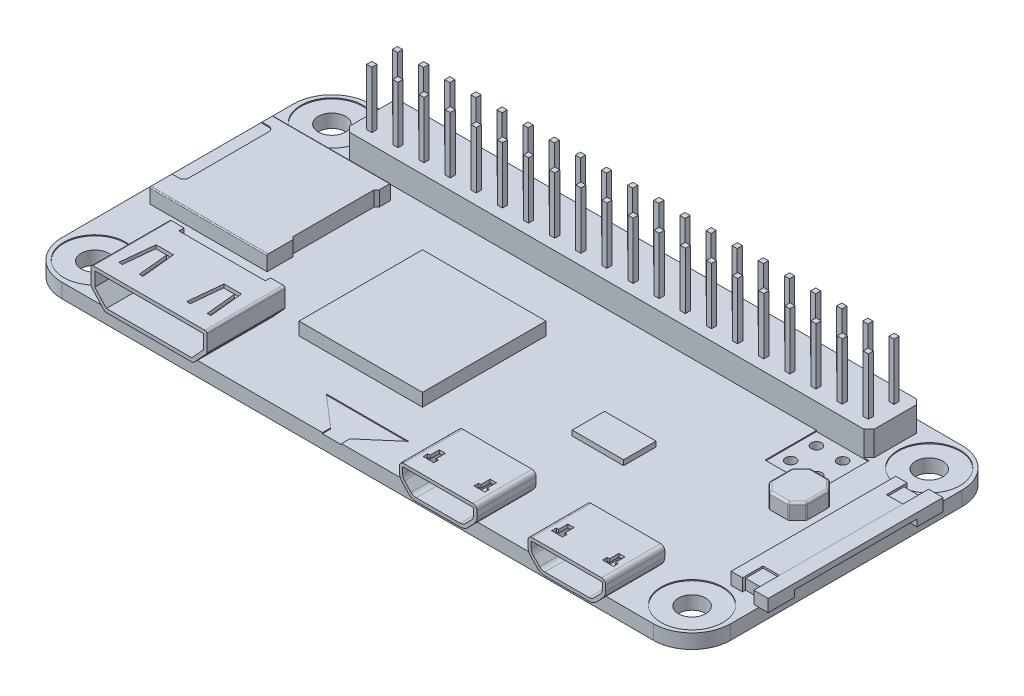
SolidWorks part; units mm, degrees
ref_plane "Front Plane" through (0, 0, 0) normal (0, 0, 1) x (1, 0, 0)
ref_plane "Top Plane" through (0, 0, 0) normal (0, 1, 0) x (1, 0, 0)
ref_plane "Right Plane" through (0, 0, 0) normal (1, 0, 0) x (0, 0, -1)
sketch "Sketch1" plane through (0, 0, 0) normal (0, 1, 0) x (1, 0, 0)
  line L1 (-28.75, 15) -> (28.75, 15)
  line L2 (-32.5, 11.25) -> (-32.5, -11.25)
  line L3 (-28.75, -15) -> (28.75, -15)
  line L4 (32.5, 11.25) -> (32.5, -11.25)
  line L5 (-32.5, 15) -> (32.5, -15) construction
  line L6 (-32.5, -15) -> (32.5, 15) construction
  arc A0 (-32.5, -11.25) -> (-28.75, -15) centre (-28.75, -11.25) ccw
  arc A1 (28.75, -15) -> (32.5, -11.25) centre (28.75, -11.25) ccw
  arc A2 (28.75, 15) -> (32.5, 11.25) centre (28.75, 11.25) cw
  arc A3 (-28.75, 15) -> (-32.5, 11.25) centre (-28.75, 11.25) ccw
  point P0 (0, 0)
  dimension "D3" = 3.75
  dimension "D1" = 65
  dimension "D2" = 30
extrude "Boss-Extrude1" add sketch "Sketch1" along normal blind 1.4 contours L1 A2 L4 A1 L3 A0 L2 A3
sketch "Sketch2" plane through (0, 1.4, 0) normal (0, 1, 0) x (1, 0, 0)
  line L0 (0, 15) -> (0, -15) construction
  line L1 (-28.75, 15) -> (28.75, 15) construction
  line L2 (-28.75, -15) -> (28.75, -15) construction
  line L3 (-32.5, 0) -> (32.5, 0) construction
  line L4 (-32.5, 11.25) -> (-32.5, -11.25) construction
  line L5 (32.5, 11.25) -> (32.5, -11.25) construction
  circle A0 centre (-29.025, 11.525) radius 1.325
  circle A2 centre (29.025, 11.525) radius 1.325
  circle A3 centre (29.025, -11.525) radius 1.325
  circle A4 centre (-29.025, -11.525) radius 1.325
  dimension "D1" = 2.65
  dimension "D2" = 2.15
  dimension "D3" = 2.15
extrude "Cut-Extrude1" cut sketch "Sketch2" against normal through all
sketch "Sketch3" plane through (0, 1.4, 0) normal (0, 1, 0) x (1, 0, 0)
  line L0 (-24.128, 13) -> (-24.128, 10.5) construction
  line L3 (-28.75, 15) -> (28.75, 15) construction
  line L5 (-32.5, 11.25) -> (-32.5, -11.25) construction
  circle A0 centre (-24.128, 13) radius 0.5
  circle A1 centre (-24.128, 10.5) radius 0.5
  dimension "D1" = 1
  dimension "D3" = 1.5
  dimension "D4" = 7.872
  dimension "D2" = 2.5
extrude "Cut-Extrude2" cut sketch "Sketch3" against normal through all
pattern_linear "LPattern1" count 20 spacing 2.54 along (1, 0, 0) of "Cut-Extrude2"
sketch "Sketch5" plane through (0, 1.4, 0) normal (0, 1, 0) x (1, 0, 0)
  line L0 (21.592, 10.5) -> (21.592, 5.5) construction
  line L1 (24.132, 10.5) -> (24.132, 5.5) construction
  line L2 (24.132, 5.5) -> (21.592, 5.5) construction
  circle A0 centre (21.592, 5.5) radius 0.5
  circle A1 centre (24.132, 5.5) radius 0.5
  circle A2 centre (21.592, 8) radius 0.5
  circle A3 centre (24.132, 8) radius 0.5
  dimension "D1" = 2.5
  dimension "D2" = 1
extrude "Cut-Extrude4" cut sketch "Sketch5" against normal through all
sketch "Sketch4" plane through (0, 1.4, 0) normal (0, 1, 0) x (1, 0, 0)
  line L0 (0, 0) -> (0, 14.3) construction
  line L1 (-24.128, 13) -> (-24.128, 10.5) construction
  line L2 (-25.5, 14.3) -> (25.5, 14.3)
  line L3 (-25.5, 14.3) -> (-25.5, 9.2)
  line L4 (-25.5, 9.2) -> (20.4, 9.2)
  line L5 (25.5, 14.3) -> (25.5, 9.2)
  line L6 (-25.5, 11.75) -> (-24.128, 11.75) construction
  line L7 (20.4, 9.2) -> (25.5, 9.2) construction
  line L8 (-2.5, -15) -> (-2.5, -11.55) construction
  line L9 (25.5, 9.2) -> (25.5, 4.2)
  line L10 (25.5, 4.2) -> (20.4, 4.2)
  line L11 (20.4, 9.2) -> (20.4, 4.2)
  line L12 (-28.75, -15) -> (28.75, -15) construction
  line L13 (-6.5, -11.55) -> (1.5, -11.55)
  line L14 (1.5, -11.55) -> (-1.575, -14.2)
  line L15 (-1.575, -14.2) -> (-1.575, -15)
  line L16 (-1.575, -15) -> (-3.425, -15)
  line L17 (-3.425, -15) -> (-3.425, -14.2)
  line L18 (-3.425, -14.2) -> (-6.5, -11.55)
  line L19 (-32.5, 11.25) -> (-32.5, -11.25) construction
  circle A0 centre (-29.025, 11.525) radius 3
  circle A1 centre (-29.025, -11.525) radius 3
  circle A2 centre (29.025, -11.525) radius 3
  circle A3 centre (29.025, 11.525) radius 3
  point P23 (-24.128, 11.75)
  point P26 (-25.5, 11.75)
  dimension "D1" = 6
  dimension "D2" = 5.1
  dimension "D3" = 51
  dimension "D4" = 5.1
  dimension "D5" = 5
  dimension "D6" = 8
  dimension "D7" = 1.85
  dimension "D8" = 3.45
  dimension "D9" = 0.8
  dimension "D10" = 30
extrude "Cut-Extrude3" cut sketch "Sketch4" against normal blind 0.1
sketch "Sketch6" plane through (0, 1.4, 0) normal (0, 1, 0) x (1, 0, 0)
  line L0 (-28.75, -15) -> (-3.425, -15) construction
  line L1 (-12.7, 4) -> (-0.7, 4)
  line L2 (-12.7, 4) -> (-12.7, -8)
  line L3 (-12.7, -8) -> (-0.7, -8)
  line L4 (-0.7, 4) -> (-0.7, -8)
  line L5 (-12.7, 4) -> (-0.7, -8) construction
  line L6 (-12.7, -8) -> (-0.7, 4) construction
  line L7 (-32.5, 11.25) -> (-32.5, -11.25) construction
  point P0 (-6.7, -2)
  dimension "D1" = 12
  dimension "D2" = 7
  dimension "D3" = 19.8
extrude "Boss-Extrude2" add sketch "Sketch6" along normal blind 1.25
sketch "Sketch7" plane through (0, 1.4, 0) normal (0, 1, 0) x (1, 0, 0)
  line L0 (-19.65, 7.85) -> (-19.65, 6.75)
  line L1 (-31.05, 7.85) -> (-19.65, 7.85)
  line L2 (-31.05, 7.85) -> (-31.05, -4.15) construction
  line L3 (-31.05, -4.15) -> (-19.65, -4.15)
  line L4 (-19.65, 7.85) -> (-19.65, -4.15) construction
  line L5 (-19.65, 6.75) -> (-19.9, 6.5)
  line L6 (-19.9, 6.5) -> (-19.9, -1.4)
  line L7 (-19.9, -1.4) -> (-19.65, -1.65)
  line L8 (-19.65, -1.65) -> (-19.65, -4.15)
  line L9 (-31.05, 7.85) -> (-31.05, 6.75)
  line L10 (-31.05, 6.75) -> (-30.4, 6.75)
  line L11 (-29.9, 6.25) -> (-29.9, -1.5)
  line L12 (-30.4, -2) -> (-31.05, -2)
  line L13 (-31.05, -2) -> (-31.05, -4.15)
  line L14 (-28.75, 15) -> (28.75, 15) construction
  line L15 (-32.5, 11.25) -> (-32.5, -11.25) construction
  arc A0 (-29.9, -1.5) -> (-30.4, -2) centre (-30.4, -1.5) cw
  arc A1 (-30.4, 6.75) -> (-29.9, 6.25) centre (-30.4, 6.25) cw
  dimension "D9" = 0.5
  dimension "D1" = 11.4
  dimension "D2" = 12
  dimension "D3" = 2.5
  dimension "D4" = 1.1
  dimension "D5" = 0.25
  dimension "D6" = 1.1
  dimension "D7" = 2.15
  dimension "D8" = 1.15
  dimension "D10" = 7.15
  dimension "D11" = 1.45
extrude "Boss-Extrude3" add sketch "Sketch7" along normal blind 1.45
fillet "Fillet2" radius 0.1 2 edges at (-25.35, 2.85, -7.85) (-25.35, 2.85, 4.15)
sketch "Sketch8" plane through (-29.9, 0, 0) normal (-1, 0, 0) x (0, 0, 1)
  line L0 (-7.85, 2.75) -> (-7.85, 1.4) construction
  line L1 (-7.75, 2.75) -> (4.05, 2.75)
  line L2 (-7.75, 2.75) -> (-7.75, 1.5)
  line L3 (-7.75, 1.5) -> (4.05, 1.5)
  line L4 (4.05, 2.75) -> (4.05, 1.5)
  line L5 (-6.25, 2.85) -> (1.5, 2.85) construction
  line L6 (4.15, 2.75) -> (4.15, 1.4) construction
  line L7 (-6.25, 1.4) -> (1.5, 1.4) construction
  dimension "D1" = 0.1
  dimension "D2" = 0.1
  dimension "D3" = 0.1
  dimension "D4" = 0.1
extrude "Cut-Extrude5" cut sketch "Sketch8" against normal blind 9.5 and the other way through all
sketch "Sketch9" plane through (0, 0, 15) normal (0, 0, 1) x (1, 0, 0)
  line L0 (-19.875, 1.4) -> (-19.875, 4.7) construction
  line L1 (-28.75, 1.4) -> (-3.425, 1.4) construction
  line L2 (-25.5, 4.7) -> (-14.25, 4.7)
  line L3 (-14.25, 4.7) -> (-14.25, 2.85)
  line L4 (-14.25, 2.85) -> (-15.575, 1.4)
  line L5 (-12.7, 1.4) -> (-0.7, 1.4) construction
  line L6 (-15.575, 1.4) -> (-24.175, 1.4)
  line L7 (-24.175, 1.4) -> (-25.5, 2.85)
  line L8 (-25.5, 2.85) -> (-25.5, 4.7)
  line L9 (-32.5, 1.4) -> (-32.5, 0) construction
  dimension "D1" = 3.3
  dimension "D2" = 1.85
  dimension "D3" = 8.6
  dimension "D4" = 11.25
  dimension "D5" = 7
extrude "Boss-Extrude4" add sketch "Sketch9" along normal blind 0.4 and the other way blind 7.2 separate body
fillet "Fillet1" radius 0.2 6 edges at (-15.575, 1.4, 11.6) (-24.175, 1.4, 11.6) (-25.5, 2.85, 11.6) (-14.25, 2.85, 11.6) (-25.5, 4.7, 11.6) (-14.25, 4.7, 11.6)
sketch "Sketch10" plane through (0, 0, 15.4) normal (0, 0, 1) x (1, 0, 0)
  line L12 (-25.15, 4.35) -> (-25.15, 2.9858)
  line L13 (-25.15, 2.9858) -> (-24.0207, 1.75)
  line L14 (-24.0207, 1.75) -> (-15.7293, 1.75)
  line L15 (-15.7293, 1.75) -> (-14.6, 2.9858)
  line L16 (-14.6, 2.9858) -> (-14.6, 4.35)
  line L17 (-14.6, 4.35) -> (-25.15, 4.35)
  line L18 (-25.15, 4.35) -> (-25.15, 2.9858)
  line L19 (-25.15, 2.9858) -> (-24.0207, 1.75)
  line L20 (-24.0207, 1.75) -> (-15.7293, 1.75)
  line L21 (-15.7293, 1.75) -> (-14.6, 2.9858)
  line L22 (-14.6, 2.9858) -> (-14.6, 4.35)
  line L23 (-14.6, 4.35) -> (-25.15, 4.35)
  dimension "D1" = 0.35
extrude "Cut-Extrude6" cut sketch "Sketch10" against normal blind 7
sketch "Sketch11" plane through (0, 0, 8.4) normal (0, 0, 1) x (1, 0, 0)
  line L0 (-19.875, 3.5) -> (-19.875, 1.75) construction
  line L1 (-23.375, 2.95) -> (-16.375, 2.95)
  line L2 (-23.375, 2.95) -> (-23.375, 3.5)
  line L3 (-23.375, 3.5) -> (-16.375, 3.5)
  line L4 (-16.375, 2.95) -> (-16.375, 3.5)
  line L5 (-24.0207, 1.75) -> (-15.7293, 1.75) construction
  line L6 (-24.0207, 1.75) -> (-15.7293, 1.75) construction
  dimension "D1" = 7
  dimension "D2" = 0.55
  dimension "D3" = 1.2
extrude "Boss-Extrude5" add sketch "Sketch11" along normal blind 3.5
sketch "Sketch12" plane through (0, 4.35, 0) normal (0, -1, 0) x (1, 0, 0)
  line L0 (-19.875, 7.8) -> (-19.875, 15.4) construction
  line L1 (-14.45, 7.8) -> (-25.3, 7.8) construction
  line L2 (-14.45, 15.4) -> (-25.3, 15.4) construction
  line L3 (-23.175, 10.57) -> (-23.175, 13.4458) construction
  line L4 (-24.025, 10.57) -> (-22.325, 10.57)
  line L5 (-22.325, 10.57) -> (-22, 13.87)
  line L6 (-22, 13.87) -> (-22.3517, 13.87)
  line L7 (-22.3517, 13.87) -> (-22.6422, 10.92)
  line L8 (-22.6422, 10.92) -> (-23.7078, 10.92)
  line L9 (-23.9983, 13.87) -> (-23.7078, 10.92)
  line L10 (-24.35, 13.87) -> (-23.9983, 13.87)
  line L11 (-24.025, 10.57) -> (-24.35, 13.87)
  line L12 (-16.575, 10.57) -> (-16.575, 13.4458) construction
  line L13 (-15.725, 10.57) -> (-15.4, 13.87)
  line L14 (-15.4, 13.87) -> (-15.7517, 13.87)
  line L15 (-15.7517, 13.87) -> (-16.0422, 10.92)
  line L16 (-17.1078, 10.92) -> (-16.0422, 10.92)
  line L17 (-17.3983, 13.87) -> (-17.1078, 10.92)
  line L18 (-17.75, 13.87) -> (-17.3983, 13.87)
  line L19 (-17.425, 10.57) -> (-17.75, 13.87)
  line L20 (-15.725, 10.57) -> (-17.425, 10.57)
  point P15 (-23.175, 10.92)
  point P28 (-16.575, 10.92)
  dimension "D1" = 0.35
  dimension "D2" = 0.35
  dimension "D3" = 3.3
  dimension "D4" = 2.35
  dimension "D5" = 1.7
  dimension "D6" = 2.77
  dimension "D7" = 4.25
extrude "Cut-Extrude7" cut sketch "Sketch12" against normal through all
sketch "Sketch13" plane through (0, 0, 7.8) normal (0, 0, -1) x (-1, 0, 0)
  line L0 (14.45, 4.7) -> (25.3, 4.7) construction
  line L1 (15.675, 4.7) -> (24.075, 4.7)
  line L2 (15.675, 4.7) -> (15.675, 3.3)
  line L3 (15.675, 3.3) -> (24.075, 3.3)
  line L4 (24.075, 4.7) -> (24.075, 3.3)
  line L5 (19.875, 1.4) -> (19.875, 4.7) construction
  line L6 (24.0868, 1.4) -> (15.6632, 1.4) construction
  dimension "D1" = 8.4
  dimension "D2" = 1.4
extrude "Cut-Extrude8" cut sketch "Sketch13" against normal blind 0.5
sketch "Sketch15" plane through (0, 0, 15) normal (0, 0, 1) x (1, 0, 0)
  line L0 (21.575, 1.4) -> (21.575, 4) construction
  line L1 (-1.575, 1.4) -> (28.75, 1.4) construction
  line L2 (18.2, 4) -> (24.95, 4)
  line L3 (25.35, 3.6) -> (25.35, 3.0523)
  line L4 (25.0714, 2.3598) -> (24.4452, 1.7075)
  line L5 (23.7238, 1.4) -> (19.4262, 1.4)
  line L6 (32.5, 1.4) -> (32.5, 0) construction
  line L7 (18.0786, 2.3598) -> (18.7048, 1.7075)
  line L8 (17.8, 3.6) -> (17.8, 3.0523)
  line L9 (15.325, 0) -> (15.325, 5.5788) construction
  line L10 (-28.75, 0) -> (28.75, 0) construction
  line L11 (9.075, 1.4) -> (9.075, 4) construction
  line L12 (12.85, 3.6) -> (12.85, 3.0523)
  line L13 (12.5714, 2.3598) -> (11.9452, 1.7075)
  line L14 (6.9262, 1.4) -> (11.2238, 1.4)
  line L15 (5.5786, 2.3598) -> (6.2048, 1.7075)
  line L16 (5.3, 3.6) -> (5.3, 3.0523)
  line L17 (12.45, 4) -> (5.7, 4)
  arc A0 (24.4452, 1.7075) -> (23.7238, 1.4) centre (23.7238, 2.4) cw
  arc A1 (18.7048, 1.7075) -> (19.4262, 1.4) centre (19.4262, 2.4) ccw
  arc A2 (25.35, 3.0523) -> (25.0714, 2.3598) centre (24.35, 3.0523) cw
  arc A3 (18.0786, 2.3598) -> (17.8, 3.0523) centre (18.8, 3.0523) cw
  arc A4 (24.95, 4) -> (25.35, 3.6) centre (24.95, 3.6) cw
  arc A5 (17.8, 3.6) -> (18.2, 4) centre (18.2, 3.6) cw
  arc A6 (12.85, 3.6) -> (12.45, 4) centre (12.45, 3.6) ccw
  arc A7 (5.7, 4) -> (5.3, 3.6) centre (5.7, 3.6) ccw
  arc A8 (12.5714, 2.3598) -> (12.85, 3.0523) centre (11.85, 3.0523) ccw
  arc A9 (5.3, 3.0523) -> (5.5786, 2.3598) centre (6.3, 3.0523) ccw
  arc A10 (11.9452, 1.7075) -> (11.2238, 1.4) centre (11.2238, 2.4) cw
  arc A11 (6.2048, 1.7075) -> (6.9262, 1.4) centre (6.9262, 2.4) ccw
  point P14 (24.15, 1.4)
  point P17 (19, 1.4)
  point P20 (25.35, 2.65)
  point P23 (17.8, 2.65)
  point P26 (25.35, 4)
  point P29 (17.8, 4)
  point P54 (12.85, 4)
  point P55 (5.3, 4)
  point P56 (12.85, 2.65)
  point P57 (5.3, 2.65)
  point P58 (11.65, 1.4)
  point P59 (6.5, 1.4)
  dimension "D6" = 1
  dimension "D7" = 0.4
  dimension "D1" = 7.55
  dimension "D2" = 2.6
  dimension "D3" = 1.35
  dimension "D4" = 5.15
  dimension "D5" = 7.15
  dimension "D8" = 4.95
extrude "Boss-Extrude6" add sketch "Sketch15" along normal blind 1.25 and the other way blind 4.5
sketch "Sketch16" plane through (0, 0, 16.25) normal (0, 0, 1) x (1, 0, 0)
  line L12 (12.45, 3.68) -> (5.7, 3.68)
  line L13 (5.62, 3.6) -> (5.62, 3.0523)
  line L14 (5.8095, 2.5814) -> (6.4357, 1.9291)
  line L15 (6.9262, 1.72) -> (11.2238, 1.72)
  line L16 (11.7143, 1.9291) -> (12.3405, 2.5814)
  line L17 (12.53, 3.0523) -> (12.53, 3.6)
  line L18 (12.45, 3.68) -> (5.7, 3.68)
  line L19 (5.62, 3.6) -> (5.62, 3.0523)
  line L20 (5.8095, 2.5814) -> (6.4357, 1.9291)
  line L21 (6.9262, 1.72) -> (11.2238, 1.72)
  line L22 (11.7143, 1.9291) -> (12.3405, 2.5814)
  line L23 (12.53, 3.0523) -> (12.53, 3.6)
  line L30 (24.2143, 1.9291) -> (24.8405, 2.5814)
  line L31 (25.03, 3.0523) -> (25.03, 3.6)
  line L32 (24.95, 3.68) -> (18.2, 3.68)
  line L33 (18.12, 3.6) -> (18.12, 3.0523)
  line L34 (18.3095, 2.5814) -> (18.9357, 1.9291)
  line L35 (19.4262, 1.72) -> (23.7238, 1.72)
  line L36 (24.2143, 1.9291) -> (24.8405, 2.5814)
  line L37 (25.03, 3.0523) -> (25.03, 3.6)
  line L38 (24.95, 3.68) -> (18.2, 3.68)
  line L39 (18.12, 3.6) -> (18.12, 3.0523)
  line L40 (18.3095, 2.5814) -> (18.9357, 1.9291)
  line L41 (19.4262, 1.72) -> (23.7238, 1.72)
  arc A12 (12.53, 3.6) -> (12.45, 3.68) centre (12.45, 3.6) ccw
  arc A13 (5.7, 3.68) -> (5.62, 3.6) centre (5.7, 3.6) ccw
  arc A14 (5.62, 3.0523) -> (5.8095, 2.5814) centre (6.3, 3.0523) ccw
  arc A15 (6.4357, 1.9291) -> (6.9262, 1.72) centre (6.9262, 2.4) ccw
  arc A16 (11.2238, 1.72) -> (11.7143, 1.9291) centre (11.2238, 2.4) ccw
  arc A17 (12.3405, 2.5814) -> (12.53, 3.0523) centre (11.85, 3.0523) ccw
  arc A18 (12.53, 3.6) -> (12.45, 3.68) centre (12.45, 3.6) ccw
  arc A19 (5.7, 3.68) -> (5.62, 3.6) centre (5.7, 3.6) ccw
  arc A20 (5.62, 3.0523) -> (5.8095, 2.5814) centre (6.3, 3.0523) ccw
  arc A21 (6.4357, 1.9291) -> (6.9262, 1.72) centre (6.9262, 2.4) ccw
  arc A22 (11.2238, 1.72) -> (11.7143, 1.9291) centre (11.2238, 2.4) ccw
  arc A23 (12.3405, 2.5814) -> (12.53, 3.0523) centre (11.85, 3.0523) ccw
  arc A30 (23.7238, 1.72) -> (24.2143, 1.9291) centre (23.7238, 2.4) ccw
  arc A31 (24.8405, 2.5814) -> (25.03, 3.0523) centre (24.35, 3.0523) ccw
  arc A32 (25.03, 3.6) -> (24.95, 3.68) centre (24.95, 3.6) ccw
  arc A33 (18.2, 3.68) -> (18.12, 3.6) centre (18.2, 3.6) ccw
  arc A34 (18.12, 3.0523) -> (18.3095, 2.5814) centre (18.8, 3.0523) ccw
  arc A35 (18.9357, 1.9291) -> (19.4262, 1.72) centre (19.4262, 2.4) ccw
  arc A36 (23.7238, 1.72) -> (24.2143, 1.9291) centre (23.7238, 2.4) ccw
  arc A37 (24.8405, 2.5814) -> (25.03, 3.0523) centre (24.35, 3.0523) ccw
  arc A38 (25.03, 3.6) -> (24.95, 3.68) centre (24.95, 3.6) ccw
  arc A39 (18.2, 3.68) -> (18.12, 3.6) centre (18.2, 3.6) ccw
  arc A40 (18.12, 3.0523) -> (18.3095, 2.5814) centre (18.8, 3.0523) ccw
  arc A41 (18.9357, 1.9291) -> (19.4262, 1.72) centre (19.4262, 2.4) ccw
  dimension "D1" = 0.32
  dimension "D2" = 0.32
extrude "Cut-Extrude9" cut sketch "Sketch16" against normal blind 5.25
sketch "Sketch17" plane through (0, 0, 11) normal (0, 0, 1) x (1, 0, 0)
  line L0 (12.85, 3.3262) -> (17.8, 3.3262) construction
  line L1 (12.85, 3.0523) -> (12.85, 3.6) construction
  line L2 (17.8, 3.6) -> (17.8, 3.0523) construction
  line L3 (15.325, 3.3262) -> (15.325, 1.4) construction
  line L4 (11.2238, 1.4) -> (19.4262, 1.4) construction
  line L5 (9.075, 1.72) -> (9.075, 3.68) construction
  line L6 (6.9262, 1.72) -> (11.2238, 1.72) construction
  line L7 (12.45, 3.68) -> (5.7, 3.68) construction
  line L8 (6.9262, 1.72) -> (11.2238, 1.72) construction
  line L9 (7.5, 3.32) -> (10.65, 3.32)
  line L10 (7.5, 3.32) -> (7.5, 2.92)
  line L11 (7.5, 2.92) -> (10.65, 2.92)
  line L12 (10.65, 3.32) -> (10.65, 2.92)
  line L13 (7.5, 3.32) -> (10.65, 2.92) construction
  line L14 (7.5, 2.92) -> (10.65, 3.32) construction
  line L15 (23.15, 2.92) -> (20, 3.32) construction
  line L16 (23.15, 3.32) -> (20, 2.92) construction
  line L17 (20, 3.32) -> (20, 2.92)
  line L18 (23.15, 2.92) -> (20, 2.92)
  line L19 (23.15, 3.32) -> (23.15, 2.92)
  line L20 (23.15, 3.32) -> (20, 3.32)
  point P16 (9.075, 3.12)
  point P27 (21.575, 3.12)
  dimension "D1" = 3.15
  dimension "D2" = 0.4
  dimension "D3" = 1.4
extrude "Boss-Extrude7" add sketch "Sketch17" along normal blind 3.5
sketch "Sketch18" plane through (0, 4, 0) normal (0, 1, 0) x (1, 0, 0)
  line L0 (9.075, -16.25) -> (9.075, -10.5) construction
  line L1 (12.45, -16.25) -> (5.7, -16.25) construction
  line L2 (6.9262, -10.5) -> (11.2238, -10.5) construction
  line L3 (12.85, -16.25) -> (17.8, -16.25) construction
  line L4 (15.325, -16.25) -> (15.325, -10.5) construction
  line L5 (6.6, -13.37) -> (6.6, -14.72) construction
  line L6 (6.9, -13.37) -> (6.3, -13.37)
  line L7 (6.3, -13.37) -> (6.3, -14.27)
  line L8 (6.3, -14.27) -> (6.075, -14.27)
  line L9 (6.075, -14.27) -> (6.075, -14.72)
  line L10 (6.075, -14.72) -> (7.125, -14.72)
  line L11 (7.125, -14.27) -> (7.125, -14.72)
  line L12 (6.9, -14.27) -> (7.125, -14.27)
  line L13 (6.9, -13.37) -> (6.9, -14.27)
  line L14 (11.55, -13.37) -> (11.55, -14.72) construction
  line L15 (11.25, -13.37) -> (11.25, -14.27)
  line L16 (11.25, -14.27) -> (11.025, -14.27)
  line L17 (11.025, -14.27) -> (11.025, -14.72)
  line L18 (12.075, -14.72) -> (11.025, -14.72)
  line L19 (12.075, -14.27) -> (12.075, -14.72)
  line L20 (11.85, -14.27) -> (12.075, -14.27)
  line L21 (11.85, -13.37) -> (11.85, -14.27)
  line L22 (11.25, -13.37) -> (11.85, -13.37)
  line L23 (19.1, -13.37) -> (19.1, -14.72) construction
  line L24 (24.05, -13.37) -> (24.05, -14.72) construction
  line L25 (21.575, -16.25) -> (21.575, -10.5) construction
  line L26 (19.4, -13.37) -> (18.8, -13.37)
  line L27 (18.8, -13.37) -> (18.8, -14.27)
  line L28 (18.8, -14.27) -> (18.575, -14.27)
  line L29 (18.575, -14.27) -> (18.575, -14.72)
  line L30 (18.575, -14.72) -> (19.625, -14.72)
  line L31 (19.625, -14.27) -> (19.625, -14.72)
  line L32 (19.4, -14.27) -> (19.625, -14.27)
  line L33 (19.4, -13.37) -> (19.4, -14.27)
  line L34 (23.75, -13.37) -> (23.75, -14.27)
  line L35 (23.75, -14.27) -> (23.525, -14.27)
  line L36 (23.525, -14.27) -> (23.525, -14.72)
  line L37 (24.575, -14.72) -> (23.525, -14.72)
  line L38 (24.575, -14.27) -> (24.575, -14.72)
  line L39 (24.35, -14.27) -> (24.575, -14.27)
  line L40 (24.35, -13.37) -> (24.35, -14.27)
  line L41 (23.75, -13.37) -> (24.35, -13.37)
  dimension "D1" = 1.05
  dimension "D2" = 1.35
  dimension "D3" = 0.9
  dimension "D4" = 0.6
  dimension "D5" = 3.9
  dimension "D6" = 1.53
extrude "Cut-Extrude10" cut sketch "Sketch18" against normal up to surface (0.32 mm away) up to face at (9.075, 3.68, 13.625)
sketch "Sketch19" plane through (32.5, 0, 0) normal (1, 0, 0) x (0, 0, -1)
  line L0 (0, 1.4) -> (0, 2.6) construction
  line L1 (11.25, 1.4) -> (-11.25, 1.4) construction
  line L2 (-8.5, 2.6) -> (8.5, 2.6)
  line L3 (8.5, 2.6) -> (8.5, 1.4)
  line L4 (6.5, 1.4) -> (6.75, 1.4) construction
  line L5 (8.5, 1.4) -> (5.95, 1.4)
  line L6 (-1.4, 1.4) -> (6.5, 1.4) construction
  line L7 (5.95, 1.4) -> (5.95, 2.05)
  line L8 (5.95, 2.05) -> (-5.95, 2.05)
  line L9 (-5.95, 2.05) -> (-5.95, 1.4)
  line L10 (-5.95, 1.4) -> (-8.5, 1.4)
  line L11 (-8, 1.4) -> (4, 1.4) construction
  line L12 (-8.5, 1.4) -> (-8.5, 2.6)
  line L13 (15, 1.4) -> (15, 0) construction
  dimension "D1" = 1.2
  dimension "D2" = 0.55
  dimension "D3" = 11.9
  dimension "D4" = 17
  dimension "D5" = 6.5
extrude "Boss-Extrude8" add sketch "Sketch19" along normal blind 0.9 and the other way blind 0.5
sketch "Sketch20" plane through (0, 1.4, 0) normal (0, 1, 0) x (1, 0, 0)
  line L0 (33.4, 0) -> (29.3, 0) construction
  line L1 (33.4, 8.5) -> (33.4, -8.5) construction
  line L2 (32, 6) -> (30.4, 6)
  line L3 (32, 8.5) -> (32, -8.5) construction
  line L4 (30.4, 6) -> (30.4, 8)
  line L5 (30.4, 8) -> (29.3, 8)
  line L6 (29.3, 8) -> (29.3, -8)
  line L7 (29.3, -8) -> (30.4, -8)
  line L8 (30.4, -8) -> (30.4, -6)
  line L9 (30.4, -6) -> (32, -6)
  line L10 (32, -6) -> (32, 6)
  dimension "D1" = 16
  dimension "D2" = 2.7
  dimension "D3" = 1.1
  dimension "D4" = 12
extrude "Boss-Extrude9" add sketch "Sketch20" along normal blind 1.19
sketch "Sketch21" plane through (0, 1.4, 0) normal (0, 1, 0) x (1, 0, 0)
  line L0 (32, 6) -> (32, 8.5) construction
  line L1 (30.4, 6) -> (32, 6)
  line L2 (30.4, 6) -> (30.4, 7.7)
  line L3 (30.4, 7.7) -> (32, 7.7)
  line L4 (32, 6) -> (32, 7.7)
  line L5 (32, 8.5) -> (32, -8.5) construction
  line L6 (30.4, -6) -> (32, -6)
  line L7 (30.4, -6) -> (30.4, -7.7)
  line L8 (30.4, -7.7) -> (32, -7.7)
  line L9 (32, -6) -> (32, -7.7)
  dimension "D1" = 1.7
extrude "Boss-Extrude10" add sketch "Sketch21" along normal blind 1
sketch "Sketch22" plane through (0, 1.4, 0) normal (0, 1, 0) x (1, 0, 0)
  line L0 (32.5, -8.5) -> (32.5, -11.25) construction
  line L1 (23.85, 4.25) -> (27.5, 4.25)
  line L2 (23.85, 4.25) -> (23.85, 0.25)
  line L3 (23.85, 0.25) -> (27.5, 0.25)
  line L4 (27.5, 4.25) -> (27.5, 0.25)
  line L5 (-28.75, 15) -> (28.75, 15) construction
  dimension "D1" = 3.65
  dimension "D2" = 4
  dimension "D3" = 5
  dimension "D4" = 10.75
extrude "Boss-Extrude11" add sketch "Sketch22" along normal blind 1.5
chamfer "Chamfer1" distance 0.9 angle 45 4 edges at (23.85, 2.15, -4.25) (27.5, 2.15, -4.25) (27.5, 2.15, -0.25) (23.85, 2.15, -0.25)
sketch "Sketch23" plane through (0, 1.4, 0) normal (0, 1, 0) x (1, 0, 0)
  line L0 (-28.75, 15) -> (28.75, 15) construction
  line L1 (9, 0) -> (14, 0)
  line L2 (9, 0) -> (9, -3.15)
  line L3 (9, -3.15) -> (14, -3.15)
  line L4 (14, 0) -> (14, -3.15)
  line L5 (32.5, -8.5) -> (32.5, -11.25) construction
  dimension "D1" = 5
  dimension "D2" = 3.15
  dimension "D3" = 15
  dimension "D4" = 18.5
extrude "Boss-Extrude12" add sketch "Sketch23" along normal blind 0.5
fillet "Fillet3" radius 0.2 16 edges at (27.05, 2.9, -3.8) (27.5, 2.9, -2.25) (27.05, 2.9, -0.7) (25.675, 2.9, -0.25) (24.3, 2.9, -0.7) (23.85, 2.9, -2.25) (24.3, 2.9, -3.8) (25.675, 2.9, -4.25) (26.6, 2.15, -4.25) (24.75, 2.15, -4.25) (23.85, 2.15, -3.35) (24.75, 2.15, -0.25) (23.85, 2.15, -1.15) (27.5, 2.15, -3.35) (27.5, 2.15, -1.15) (26.6, 2.15, -0.25)
sketch "草图1" plane through (0, 0, 0) normal (0, -1, 0) x (1, 0, 0)
  circle A0 centre (22.059, 8.8833) radius 0.75
  circle A1 centre (22.059, 11.1732) radius 0.75
  circle A2 centre (8.3246, 12.8981) radius 0.6
  circle A3 centre (10.1975, 12.8981) radius 0.6
  dimension "D1" = 1.5
  dimension "D2" = 1.2
extrude "凸台-拉伸1" add sketch "草图1" along normal blind 0.1
sketch "草图2" plane through (0, 1.3, 0) normal (0, 1, 0) x (1, 0, 0)
  line L0 (-21.838, 13.25) -> (-21.338, 13.25)
  line L1 (-24.378, 13.25) -> (-23.878, 13.25)
  line L2 (-24.378, 13.25) -> (-24.378, 12.75)
  line L3 (-24.378, 12.75) -> (-23.878, 12.75)
  line L4 (-23.878, 13.25) -> (-23.878, 12.75)
  line L5 (-24.378, 13.25) -> (-23.878, 12.75) construction
  line L6 (-24.378, 12.75) -> (-23.878, 13.25) construction
  line L7 (-21.838, 13.25) -> (-21.838, 12.75)
  line L8 (-21.838, 12.75) -> (-21.338, 12.75)
  line L9 (-21.338, 13.25) -> (-21.338, 12.75)
  line L10 (-21.838, 13.25) -> (-21.338, 12.75) construction
  line L11 (-21.838, 12.75) -> (-21.338, 13.25) construction
  line L12 (-19.298, 13.25) -> (-18.798, 13.25)
  line L13 (-19.298, 13.25) -> (-19.298, 12.75)
  line L14 (-19.298, 12.75) -> (-18.798, 12.75)
  line L15 (-18.798, 13.25) -> (-18.798, 12.75)
  line L16 (-19.298, 13.25) -> (-18.798, 12.75) construction
  line L17 (-19.298, 12.75) -> (-18.798, 13.25) construction
  line L18 (-16.758, 13.25) -> (-16.258, 13.25)
  line L19 (-16.758, 13.25) -> (-16.758, 12.75)
  line L20 (-16.758, 12.75) -> (-16.258, 12.75)
  line L21 (-16.258, 13.25) -> (-16.258, 12.75)
  line L22 (-16.758, 13.25) -> (-16.258, 12.75) construction
  line L23 (-16.758, 12.75) -> (-16.258, 13.25) construction
  line L24 (-14.218, 13.25) -> (-13.718, 13.25)
  line L25 (-14.218, 13.25) -> (-14.218, 12.75)
  line L26 (-14.218, 12.75) -> (-13.718, 12.75)
  line L27 (-13.718, 13.25) -> (-13.718, 12.75)
  line L28 (-14.218, 13.25) -> (-13.718, 12.75) construction
  line L29 (-14.218, 12.75) -> (-13.718, 13.25) construction
  line L30 (-11.678, 13.25) -> (-11.178, 13.25)
  line L31 (-11.678, 13.25) -> (-11.678, 12.75)
  line L32 (-11.678, 12.75) -> (-11.178, 12.75)
  line L33 (-11.178, 13.25) -> (-11.178, 12.75)
  line L34 (-11.678, 13.25) -> (-11.178, 12.75) construction
  line L35 (-11.678, 12.75) -> (-11.178, 13.25) construction
  line L36 (-9.138, 13.25) -> (-8.638, 13.25)
  line L37 (-9.138, 13.25) -> (-9.138, 12.75)
  line L38 (-9.138, 12.75) -> (-8.638, 12.75)
  line L39 (-8.638, 13.25) -> (-8.638, 12.75)
  line L40 (-9.138, 13.25) -> (-8.638, 12.75) construction
  line L41 (-9.138, 12.75) -> (-8.638, 13.25) construction
  line L42 (-6.598, 13.25) -> (-6.098, 13.25)
  line L43 (-6.598, 13.25) -> (-6.598, 12.75)
  line L44 (-6.598, 12.75) -> (-6.098, 12.75)
  line L45 (-6.098, 13.25) -> (-6.098, 12.75)
  line L46 (-6.598, 13.25) -> (-6.098, 12.75) construction
  line L47 (-6.598, 12.75) -> (-6.098, 13.25) construction
  line L48 (-4.058, 13.25) -> (-3.558, 13.25)
  line L49 (-4.058, 13.25) -> (-4.058, 12.75)
  line L50 (-4.058, 12.75) -> (-3.558, 12.75)
  line L51 (-3.558, 13.25) -> (-3.558, 12.75)
  line L52 (-4.058, 13.25) -> (-3.558, 12.75) construction
  line L53 (-4.058, 12.75) -> (-3.558, 13.25) construction
  line L54 (-1.518, 13.25) -> (-1.018, 13.25)
  line L55 (-1.518, 13.25) -> (-1.518, 12.75)
  line L56 (-1.518, 12.75) -> (-1.018, 12.75)
  line L57 (-1.018, 13.25) -> (-1.018, 12.75)
  line L58 (-1.518, 13.25) -> (-1.018, 12.75) construction
  line L59 (-1.518, 12.75) -> (-1.018, 13.25) construction
  line L60 (1.022, 13.25) -> (1.522, 13.25)
  line L61 (1.022, 13.25) -> (1.022, 12.75)
  line L62 (1.022, 12.75) -> (1.522, 12.75)
  line L63 (1.522, 13.25) -> (1.522, 12.75)
  line L64 (1.022, 13.25) -> (1.522, 12.75) construction
  line L65 (1.022, 12.75) -> (1.522, 13.25) construction
  line L66 (3.562, 13.25) -> (4.062, 13.25)
  line L67 (3.562, 13.25) -> (3.562, 12.75)
  line L68 (3.562, 12.75) -> (4.062, 12.75)
  line L69 (4.062, 13.25) -> (4.062, 12.75)
  line L70 (3.562, 13.25) -> (4.062, 12.75) construction
  line L71 (3.562, 12.75) -> (4.062, 13.25) construction
  line L72 (6.102, 13.25) -> (6.602, 13.25)
  line L73 (6.102, 13.25) -> (6.102, 12.75)
  line L74 (6.102, 12.75) -> (6.602, 12.75)
  line L75 (6.602, 13.25) -> (6.602, 12.75)
  line L76 (6.102, 13.25) -> (6.602, 12.75) construction
  line L77 (6.102, 12.75) -> (6.602, 13.25) construction
  line L78 (8.642, 13.25) -> (9.142, 13.25)
  line L79 (8.642, 13.25) -> (8.642, 12.75)
  line L80 (8.642, 12.75) -> (9.142, 12.75)
  line L81 (9.142, 13.25) -> (9.142, 12.75)
  line L82 (8.642, 13.25) -> (9.142, 12.75) construction
  line L83 (8.642, 12.75) -> (9.142, 13.25) construction
  line L84 (11.182, 13.25) -> (11.682, 13.25)
  line L85 (11.182, 13.25) -> (11.182, 12.75)
  line L86 (11.182, 12.75) -> (11.682, 12.75)
  line L87 (11.682, 13.25) -> (11.682, 12.75)
  line L88 (11.182, 13.25) -> (11.682, 12.75) construction
  line L89 (11.182, 12.75) -> (11.682, 13.25) construction
  line L90 (13.722, 13.25) -> (14.222, 13.25)
  line L91 (13.722, 13.25) -> (13.722, 12.75)
  line L92 (13.722, 12.75) -> (14.222, 12.75)
  line L93 (14.222, 13.25) -> (14.222, 12.75)
  line L94 (13.722, 13.25) -> (14.222, 12.75) construction
  line L95 (13.722, 12.75) -> (14.222, 13.25) construction
  line L96 (16.262, 13.25) -> (16.762, 13.25)
  line L97 (16.262, 13.25) -> (16.262, 12.75)
  line L98 (16.262, 12.75) -> (16.762, 12.75)
  line L99 (16.762, 13.25) -> (16.762, 12.75)
  line L100 (16.262, 13.25) -> (16.762, 12.75) construction
  line L101 (16.262, 12.75) -> (16.762, 13.25) construction
  line L102 (18.802, 13.25) -> (19.302, 13.25)
  line L103 (18.802, 13.25) -> (18.802, 12.75)
  line L104 (18.802, 12.75) -> (19.302, 12.75)
  line L105 (19.302, 13.25) -> (19.302, 12.75)
  line L106 (18.802, 13.25) -> (19.302, 12.75) construction
  line L107 (18.802, 12.75) -> (19.302, 13.25) construction
  line L108 (21.342, 13.25) -> (21.842, 13.25)
  line L109 (21.342, 13.25) -> (21.342, 12.75)
  line L110 (21.342, 12.75) -> (21.842, 12.75)
  line L111 (21.842, 13.25) -> (21.842, 12.75)
  line L112 (21.342, 13.25) -> (21.842, 12.75) construction
  line L113 (21.342, 12.75) -> (21.842, 13.25) construction
  line L114 (23.882, 13.25) -> (24.382, 13.25)
  line L115 (23.882, 13.25) -> (23.882, 12.75)
  line L116 (23.882, 12.75) -> (24.382, 12.75)
  line L117 (24.382, 13.25) -> (24.382, 12.75)
  line L118 (23.882, 13.25) -> (24.382, 12.75) construction
  line L119 (23.882, 12.75) -> (24.382, 13.25) construction
  line L120 (-21.838, 10.75) -> (-21.338, 10.75)
  line L121 (-21.838, 10.75) -> (-21.838, 10.25)
  line L122 (-21.838, 10.25) -> (-21.338, 10.25)
  line L123 (-21.338, 10.75) -> (-21.338, 10.25)
  line L124 (-21.838, 10.75) -> (-21.338, 10.25) construction
  line L125 (-21.838, 10.25) -> (-21.338, 10.75) construction
  line L126 (-19.298, 10.75) -> (-18.798, 10.75)
  line L127 (-19.298, 10.75) -> (-19.298, 10.25)
  line L128 (-19.298, 10.25) -> (-18.798, 10.25)
  line L129 (-18.798, 10.75) -> (-18.798, 10.25)
  line L130 (-19.298, 10.75) -> (-18.798, 10.25) construction
  line L131 (-19.298, 10.25) -> (-18.798, 10.75) construction
  line L132 (-16.758, 10.75) -> (-16.258, 10.75)
  line L133 (-16.758, 10.75) -> (-16.758, 10.25)
  line L134 (-16.758, 10.25) -> (-16.258, 10.25)
  line L135 (-16.258, 10.75) -> (-16.258, 10.25)
  line L136 (-16.758, 10.75) -> (-16.258, 10.25) construction
  line L137 (-16.758, 10.25) -> (-16.258, 10.75) construction
  line L138 (-14.218, 10.75) -> (-13.718, 10.75)
  line L139 (-14.218, 10.75) -> (-14.218, 10.25)
  line L140 (-14.218, 10.25) -> (-13.718, 10.25)
  line L141 (-13.718, 10.75) -> (-13.718, 10.25)
  line L142 (-14.218, 10.75) -> (-13.718, 10.25) construction
  line L143 (-14.218, 10.25) -> (-13.718, 10.75) construction
  line L144 (-11.678, 10.75) -> (-11.178, 10.75)
  line L145 (-11.678, 10.75) -> (-11.678, 10.25)
  line L146 (-11.678, 10.25) -> (-11.178, 10.25)
  line L147 (-11.178, 10.75) -> (-11.178, 10.25)
  line L148 (-11.678, 10.75) -> (-11.178, 10.25) construction
  line L149 (-11.678, 10.25) -> (-11.178, 10.75) construction
  line L150 (-9.138, 10.75) -> (-8.638, 10.75)
  line L151 (-9.138, 10.75) -> (-9.138, 10.25)
  line L152 (-9.138, 10.25) -> (-8.638, 10.25)
  line L153 (-8.638, 10.75) -> (-8.638, 10.25)
  line L154 (-9.138, 10.75) -> (-8.638, 10.25) construction
  line L155 (-9.138, 10.25) -> (-8.638, 10.75) construction
  line L156 (-6.598, 10.75) -> (-6.098, 10.75)
  line L157 (-6.598, 10.75) -> (-6.598, 10.25)
  line L158 (-6.598, 10.25) -> (-6.098, 10.25)
  line L159 (-6.098, 10.75) -> (-6.098, 10.25)
  line L160 (-6.598, 10.75) -> (-6.098, 10.25) construction
  line L161 (-6.598, 10.25) -> (-6.098, 10.75) construction
  line L162 (-4.058, 10.75) -> (-3.558, 10.75)
  line L163 (-4.058, 10.75) -> (-4.058, 10.25)
  line L164 (-4.058, 10.25) -> (-3.558, 10.25)
  line L165 (-3.558, 10.75) -> (-3.558, 10.25)
  line L166 (-4.058, 10.75) -> (-3.558, 10.25) construction
  line L167 (-4.058, 10.25) -> (-3.558, 10.75) construction
  line L168 (-1.518, 10.75) -> (-1.018, 10.75)
  line L169 (-1.518, 10.75) -> (-1.518, 10.25)
  line L170 (-1.518, 10.25) -> (-1.018, 10.25)
  line L171 (-1.018, 10.75) -> (-1.018, 10.25)
  line L172 (-1.518, 10.75) -> (-1.018, 10.25) construction
  line L173 (-1.518, 10.25) -> (-1.018, 10.75) construction
  line L174 (1.022, 10.75) -> (1.522, 10.75)
  line L175 (1.022, 10.75) -> (1.022, 10.25)
  line L176 (1.022, 10.25) -> (1.522, 10.25)
  line L177 (1.522, 10.75) -> (1.522, 10.25)
  line L178 (1.022, 10.75) -> (1.522, 10.25) construction
  line L179 (1.022, 10.25) -> (1.522, 10.75) construction
  line L180 (3.562, 10.75) -> (4.062, 10.75)
  line L181 (3.562, 10.75) -> (3.562, 10.25)
  line L182 (3.562, 10.25) -> (4.062, 10.25)
  line L183 (4.062, 10.75) -> (4.062, 10.25)
  line L184 (3.562, 10.75) -> (4.062, 10.25) construction
  line L185 (3.562, 10.25) -> (4.062, 10.75) construction
  line L186 (6.102, 10.75) -> (6.602, 10.75)
  line L187 (6.102, 10.75) -> (6.102, 10.25)
  line L188 (6.102, 10.25) -> (6.602, 10.25)
  line L189 (6.602, 10.75) -> (6.602, 10.25)
  line L190 (6.102, 10.75) -> (6.602, 10.25) construction
  line L191 (6.102, 10.25) -> (6.602, 10.75) construction
  line L192 (8.642, 10.75) -> (9.142, 10.75)
  line L193 (8.642, 10.75) -> (8.642, 10.25)
  line L194 (8.642, 10.25) -> (9.142, 10.25)
  line L195 (9.142, 10.75) -> (9.142, 10.25)
  line L196 (8.642, 10.75) -> (9.142, 10.25) construction
  line L197 (8.642, 10.25) -> (9.142, 10.75) construction
  line L198 (11.182, 10.75) -> (11.682, 10.75)
  line L199 (11.182, 10.75) -> (11.182, 10.25)
  line L200 (11.182, 10.25) -> (11.682, 10.25)
  line L201 (11.682, 10.75) -> (11.682, 10.25)
  line L202 (11.182, 10.75) -> (11.682, 10.25) construction
  line L203 (11.182, 10.25) -> (11.682, 10.75) construction
  line L204 (13.722, 10.75) -> (14.222, 10.75)
  line L205 (13.722, 10.75) -> (13.722, 10.25)
  line L206 (13.722, 10.25) -> (14.222, 10.25)
  line L207 (14.222, 10.75) -> (14.222, 10.25)
  line L208 (13.722, 10.75) -> (14.222, 10.25) construction
  line L209 (13.722, 10.25) -> (14.222, 10.75) construction
  line L210 (16.262, 10.75) -> (16.762, 10.75)
  line L211 (16.262, 10.75) -> (16.262, 10.25)
  line L212 (16.262, 10.25) -> (16.762, 10.25)
  line L213 (16.762, 10.75) -> (16.762, 10.25)
  line L214 (16.262, 10.75) -> (16.762, 10.25) construction
  line L215 (16.262, 10.25) -> (16.762, 10.75) construction
  line L216 (18.802, 10.75) -> (19.302, 10.75)
  line L217 (18.802, 10.75) -> (18.802, 10.25)
  line L218 (18.802, 10.25) -> (19.302, 10.25)
  line L219 (19.302, 10.75) -> (19.302, 10.25)
  line L220 (18.802, 10.75) -> (19.302, 10.25) construction
  line L221 (18.802, 10.25) -> (19.302, 10.75) construction
  line L222 (21.342, 10.75) -> (21.842, 10.75)
  line L223 (21.342, 10.75) -> (21.342, 10.25)
  line L224 (21.342, 10.25) -> (21.842, 10.25)
  line L225 (21.842, 10.75) -> (21.842, 10.25)
  line L226 (21.342, 10.75) -> (21.842, 10.25) construction
  line L227 (21.342, 10.25) -> (21.842, 10.75) construction
  line L228 (23.882, 10.75) -> (24.382, 10.75)
  line L229 (23.882, 10.75) -> (23.882, 10.25)
  line L230 (23.882, 10.25) -> (24.382, 10.25)
  line L231 (24.382, 10.75) -> (24.382, 10.25)
  line L232 (23.882, 10.75) -> (24.382, 10.25) construction
  line L233 (23.882, 10.25) -> (24.382, 10.75) construction
  line L234 (-24.378, 10.75) -> (-23.878, 10.75)
  line L235 (-24.378, 10.75) -> (-24.378, 10.25)
  line L236 (-24.378, 10.25) -> (-23.878, 10.25)
  line L237 (-23.878, 10.75) -> (-23.878, 10.25)
  line L238 (-24.378, 10.75) -> (-23.878, 10.25) construction
  line L239 (-24.378, 10.25) -> (-23.878, 10.75) construction
  circle A0 centre (-24.128, 13) radius 0.5 construction
  point P0 (-24.128, 13)
  point P10 (-21.588, 13)
  point P15 (-19.048, 13)
  point P20 (-16.508, 13)
  point P25 (-13.968, 13)
  point P30 (-11.428, 13)
  point P35 (-8.888, 13)
  point P40 (-6.348, 13)
  point P45 (-3.808, 13)
  point P50 (-1.268, 13)
  point P55 (1.272, 13)
  point P60 (3.812, 13)
  point P65 (6.352, 13)
  point P70 (8.892, 13)
  point P75 (11.432, 13)
  point P80 (13.972, 13)
  point P85 (16.512, 13)
  point P90 (19.052, 13)
  point P95 (21.592, 13)
  point P100 (24.132, 13)
  point P105 (-21.588, 10.5)
  point P110 (-19.048, 10.5)
  point P115 (-16.508, 10.5)
  point P120 (-13.968, 10.5)
  point P125 (-11.428, 10.5)
  point P130 (-8.888, 10.5)
  point P135 (-6.348, 10.5)
  point P140 (-3.808, 10.5)
  point P145 (-1.268, 10.5)
  point P150 (1.272, 10.5)
  point P155 (3.812, 10.5)
  point P160 (6.352, 10.5)
  point P165 (8.892, 10.5)
  point P170 (11.432, 10.5)
  point P175 (13.972, 10.5)
  point P180 (16.512, 10.5)
  point P185 (19.052, 10.5)
  point P190 (21.592, 10.5)
  point P195 (24.132, 10.5)
  point P200 (-24.128, 10.5)
  dimension "D1" = 0.5
  dimension "D2" = 20
  dimension "D3" = 2
extrude "凸台-拉伸2" add sketch "草图2" along normal blind 8 separate body
sketch "草图3" plane through (0, 1.3, 0) normal (0, 1, 0) x (1, 0, 0)
  line L0 (25.5, 4.25) -> (25.5, 14.3) construction
  line L1 (-25.5, 14.3) -> (25.5, 14.3)
  line L2 (-25.5, 14.3) -> (-25.5, 9.2)
  line L3 (-25.5, 9.2) -> (25.5, 9.2)
  line L4 (25.5, 14.3) -> (25.5, 9.2)
  line L5 (-25.5, 9.2) -> (20.4, 9.2) construction
extrude "凸台-拉伸3" add sketch "草图3" along normal blind 2.5
chamfer "倒角1" distance 0.5 angle 45 4 edges at (25.5, 2.6, -9.2) (25.5, 2.6, -14.3) (-25.5, 2.6, -14.3) (-25.5, 2.6, -9.2)
